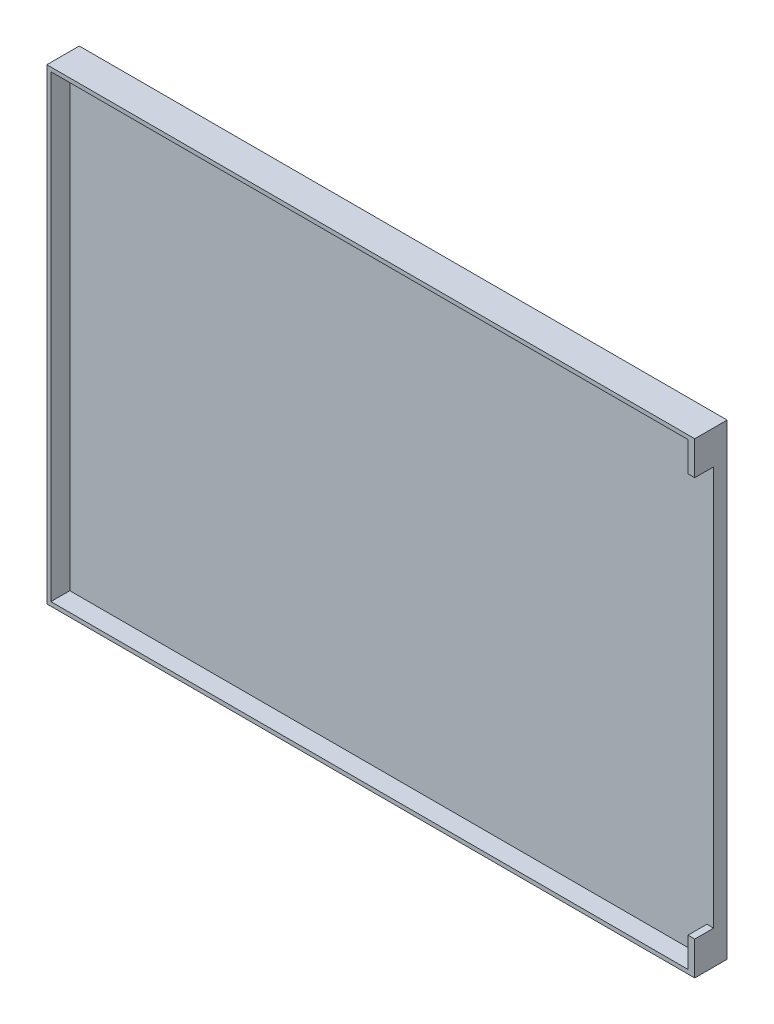
SolidWorks part; units mm, degrees
ref_plane "Спереди" through (0, 0, 0) normal (0, 0, 1) x (1, 0, 0)
ref_plane "Сверху" through (0, 0, 0) normal (0, 1, 0) x (1, 0, 0)
ref_plane "Справа" through (0, 0, 0) normal (1, 0, 0) x (0, 0, -1)
sketch "Эскиз1" plane through (0, 0, 0) normal (0, 0, 1) x (1, 0, 0)
  line L1 (-24, -17.3) -> (24, -17.3)
  line L2 (-24, -17.3) -> (-24, 17.3)
  line L3 (-24, 17.3) -> (24, 17.3)
  line L4 (24, -17.3) -> (24, 17.3)
  line L5 (-24, -17.3) -> (24, 17.3) construction
  line L6 (-24, 17.3) -> (24, -17.3) construction
  point P0 (0, 0)
  dimension "D1" = 34.6
  dimension "D2" = 48
extrude "Бобышка-Вытянуть1" add sketch "Эскиз1" along normal blind 1
sketch "Эскиз2" plane through (0, 0, 1) normal (0, 0, 1) x (1, 0, 0)
  line L4 (24, -17.3) -> (24, 17.3)
  line L5 (24, 17.3) -> (-24, 17.3)
  line L6 (-24, 17.3) -> (-24, -17.3)
  line L7 (-24, -17.3) -> (24, -17.3)
  line L9 (24, 17.3) -> (-24, 17.3)
  line L10 (-24, 17.3) -> (-24, -17.3)
  line L11 (-24, -17.3) -> (24, -17.3)
  line L12 (23.5, 17) -> (-23.7, 17)
  line L13 (-23.7, 17) -> (-23.7, -17)
  line L14 (-23.7, -17) -> (23.5, -17)
  line L15 (24, 17) -> (-23.7, 17) construction
  line L16 (-23.7, -17) -> (24, -17) construction
  line L17 (23.5, 17) -> (23.5, 14.8)
  line L18 (23.5, 14.8) -> (24, 14.8)
  line L19 (24, -17.3) -> (24, 17.3) construction
  line L20 (24, 14.8) -> (24, 17.3)
  line L21 (23.5, -17) -> (23.5, -14.8)
  line L22 (23.5, -14.8) -> (24, -14.8)
  line L23 (24, -14.8) -> (24, -17.3)
  dimension "D3" = 0.5
  dimension "D4" = 2.5
  dimension "D1" = 0
  dimension "D2" = 0.3
extrude "Бобышка-Вытянуть2" add sketch "Эскиз2" along normal blind 1.4
